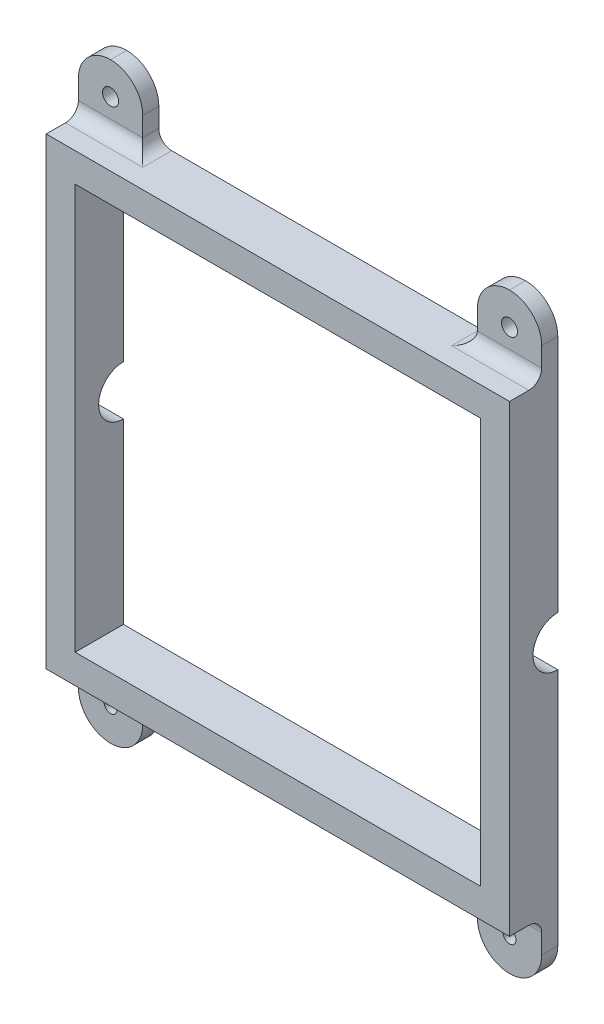
SolidWorks part; units mm, degrees
ref_plane "Front Plane" through (0, 0, 0) normal (0, 0, 1) x (1, 0, 0)
ref_plane "Top Plane" through (0, 0, 0) normal (0, 1, 0) x (1, 0, 0)
ref_plane "Right Plane" through (0, 0, 0) normal (1, 0, 0) x (0, 0, -1)
sketch "Sketch1" plane through (0, 0, 0) normal (0, 0, 1) x (1, 0, 0)
  line L1 (-45.72, -45.72) -> (45.72, -45.72)
  line L2 (-45.72, -45.72) -> (-45.72, 45.72)
  line L3 (-45.72, 45.72) -> (45.72, 45.72)
  line L4 (45.72, -45.72) -> (45.72, 45.72)
  line L5 (-45.72, -45.72) -> (45.72, 45.72) construction
  line L6 (-45.72, 45.72) -> (45.72, -45.72) construction
  point P0 (0, 0)
  dimension "D1" = 91.44
  dimension "D2" = 91.44
extrude "Boss-Extrude1" add sketch "Sketch1" along normal blind 9.525
sketch "Sketch2" plane through (0, 0, 9.525) normal (0, 0, 1) x (1, 0, 0)
  line L1 (-40.005, -40.005) -> (40.005, -40.005)
  line L2 (-40.005, -40.005) -> (-40.005, 40.005)
  line L3 (-40.005, 40.005) -> (40.005, 40.005)
  line L4 (40.005, -40.005) -> (40.005, 40.005)
  line L5 (-40.005, -40.005) -> (40.005, 40.005) construction
  line L6 (-40.005, 40.005) -> (40.005, -40.005) construction
  point P0 (0, 0)
  dimension "D1" = 80.01
  dimension "D2" = 80.01
extrude "Cut-Extrude1" cut sketch "Sketch2" against normal blind 9.525
sketch "Sketch3" plane through (45.72, 0, 0) normal (1, 0, 0) x (0, 0, -1)
  line L0 (0, -45.72) -> (0, 45.72) construction
  circle A0 centre (0, 0) radius 4.8895
  circle A1 centre (0, 57.404) radius 4.8895
  circle A2 centre (0, -57.404) radius 4.8895
  dimension "D1" = 9.779
  dimension "D2" = 9.779
  dimension "D3" = 9.779
  dimension "D4" = 57.404
  dimension "D5" = 57.404
extrude "Cut-Extrude2" cut sketch "Sketch3" against normal through all
sketch "Sketch4" plane through (0, 0, 0) normal (0, 0, -1) x (-1, 0, 0)
  line L1 (-45.72, 45.72) -> (-33.02, 45.72)
  line L2 (-45.72, 45.72) -> (-45.72, 58.42)
  line L3 (-45.72, 58.42) -> (-33.02, 58.42)
  line L4 (-33.02, 45.72) -> (-33.02, 58.42)
  dimension "D1" = 12.7
  dimension "D2" = 12.7
extrude "Boss-Extrude2" add sketch "Sketch4" against normal blind 3.175
sketch "Sketch5" plane through (0, 0, 3.175) normal (0, 0, 1) x (1, 0, 0)
  line L0 (33.02, 52.07) -> (45.72, 52.07) construction
  line L3 (39.37, 58.42) -> (39.37, 45.72) construction
  line L6 (45.72, 58.42) -> (45.72, 45.72) construction
  line L7 (33.02, 58.42) -> (45.72, 58.42) construction
  circle A0 centre (39.37, 52.07) radius 1.5875
  dimension "D4" = 3.175
  dimension "D1" = 6.35
  dimension "D2" = 6.35
  dimension "D3" = 6.35
extrude "Cut-Extrude3" cut sketch "Sketch5" against normal through all
fillet "Fillet1" radius 6.35 2 edges at (33.02, 58.42, 1.5875) (45.72, 58.42, 1.5875)
fillet "Fillet2" radius 2.54 2 edges at (33.02, 45.72, 1.5875) (39.37, 45.72, 3.175)
mirror "Mirror1" about plane through (0, 0, 0) normal (1, 0, 0) of "Boss-Extrude2", "Cut-Extrude3", "Fillet1", "Fillet2"
sketch "Sketch6" plane through (0, 0, 0) normal (0, 0, -1) x (-1, 0, 0)
  line L1 (-45.72, -45.72) -> (-33.02, -45.72)
  line L2 (-45.72, -45.72) -> (-45.72, -58.42)
  line L3 (-45.72, -58.42) -> (-33.02, -58.42)
  line L4 (-33.02, -45.72) -> (-33.02, -58.42)
  circle A0 centre (-39.37, -52.07) radius 1.27
  dimension "D5" = 2.54
  dimension "D1" = 12.7
  dimension "D2" = 12.7
  dimension "D3" = 6.35
  dimension "D4" = 6.35
extrude "Boss-Extrude3" add sketch "Sketch6" against normal blind 3.175
fillet "Fillet3" radius 2.54 2 edges at (33.02, -45.72, 1.5875) (39.37, -45.72, 3.175)
fillet "Fillet4" radius 6.35 2 edges at (45.72, -58.42, 1.5875) (33.02, -58.42, 1.5875)
mirror "Mirror7" about plane through (0, 0, 0) normal (1, 0, 0) of "Fillet4", "Fillet3", "Boss-Extrude3"
